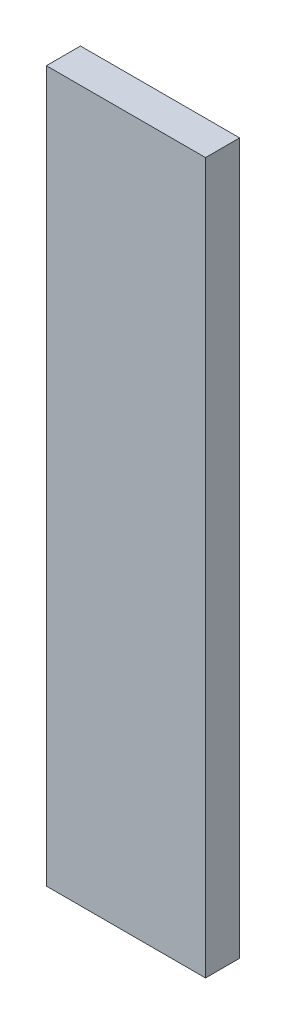
SolidWorks part; units mm, degrees
ref_plane "Alzado" through (0, 0, 0) normal (0, 0, 1) x (1, 0, 0)
ref_plane "Planta" through (0, 0, 0) normal (0, 1, 0) x (1, 0, 0)
ref_plane "Vista lateral" through (0, 0, 0) normal (1, 0, 0) x (0, 0, -1)
sketch "Croquis1" plane through (0, 0, 0) normal (0, 0, 1) x (1, 0, 0)
  line L1 (0, 0) -> (28, 0)
  line L2 (0, 0) -> (0, 125)
  line L3 (0, 125) -> (28, 125)
  line L4 (28, 0) -> (28, 125)
  dimension "D1" = 28
  dimension "D2" = 125
extrude "Saliente-Extruir1" add sketch "Croquis1" along normal blind 6
